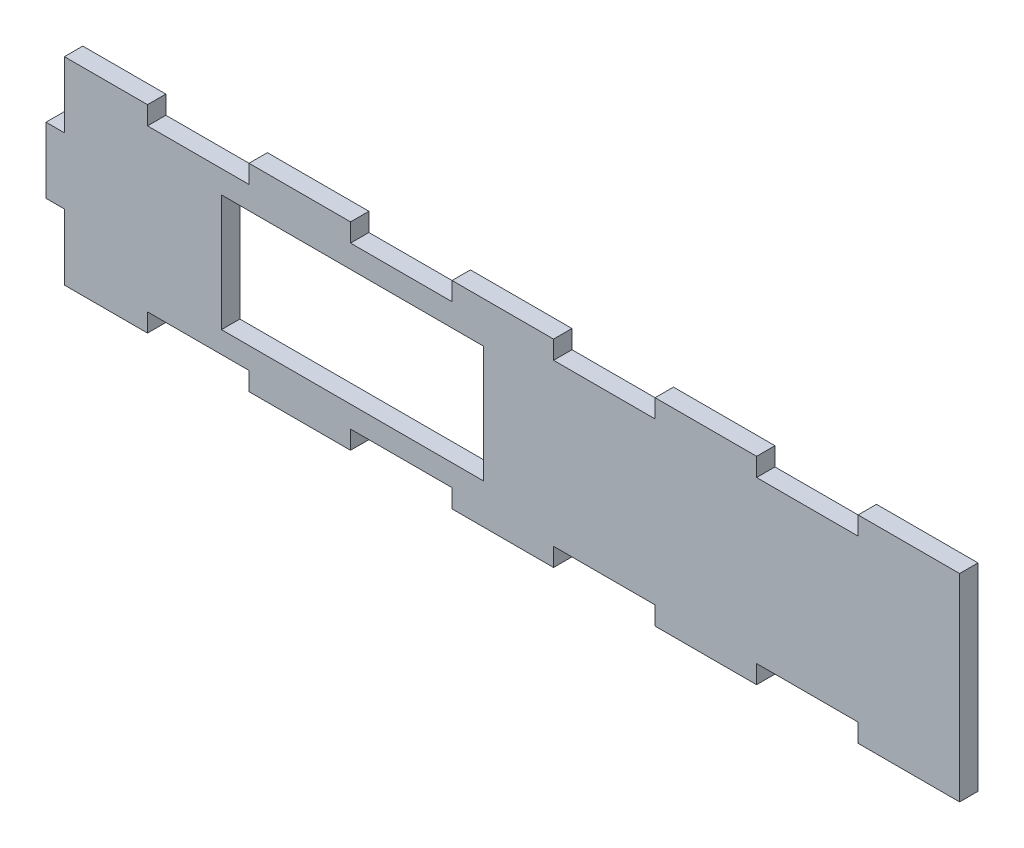
SolidWorks part; units mm, degrees
ref_plane "Front Plane" through (0, 0, 0) normal (0, 0, 1) x (1, 0, 0)
ref_plane "Top Plane" through (0, 0, 0) normal (0, 1, 0) x (1, 0, 0)
ref_plane "Right Plane" through (0, 0, 0) normal (1, 0, 0) x (0, 0, -1)
sketch "Sketch2" plane through (0, 0, 0) normal (0, 0, 1) x (1, 0, 0)
  line L1 (0, 0) -> (228.6, 0)
  line L2 (0, 0) -> (0, 49.5)
  line L3 (0, 49.5) -> (228.6, 49.5)
  line L4 (228.6, 0) -> (228.6, 49.5)
  line L5 (0, 0) -> (228.6, 49.5) construction
  line L6 (0, 49.5) -> (228.6, 0) construction
  point P4 (114.3, 24.75)
  dimension "D1" = 228.6
  dimension "D2" = 49.5
extrude "Boss-Extrude1" add sketch "Sketch2" along normal blind 4.6
sketch "Sketch4" plane through (0, 0, 4.6) normal (0, 0, 1) x (1, 0, 0)
  line L0 (0, 0) -> (228.6, 0) construction
  line L1 (25.4, 0) -> (50.8, 0)
  line L2 (25.4, 0) -> (25.4, 4.6)
  line L3 (25.4, 4.6) -> (50.8, 4.6)
  line L4 (50.8, 0) -> (50.8, 4.6)
  line L5 (25.4, 0) -> (50.8, 4.6) construction
  line L6 (25.4, 4.6) -> (50.8, 0) construction
  line L7 (0, 0) -> (25.4, 0) construction
  line L8 (76.2, 0) -> (101.6, 0)
  line L9 (76.2, 0) -> (76.2, 4.6)
  line L10 (76.2, 4.6) -> (101.6, 4.6)
  line L11 (101.6, 0) -> (101.6, 4.6)
  line L12 (76.2, 0) -> (101.6, 4.6) construction
  line L13 (76.2, 4.6) -> (101.6, 0) construction
  line L14 (127, 0) -> (152.4, 0)
  line L15 (127, 0) -> (127, 4.6)
  line L16 (127, 4.6) -> (152.4, 4.6)
  line L17 (152.4, 0) -> (152.4, 4.6)
  line L18 (127, 0) -> (152.4, 4.6) construction
  line L19 (127, 4.6) -> (152.4, 0) construction
  line L20 (177.8, 0) -> (203.2, 0)
  line L21 (177.8, 0) -> (177.8, 4.6)
  line L22 (177.8, 4.6) -> (203.2, 4.6)
  line L23 (203.2, 0) -> (203.2, 4.6)
  line L24 (177.8, 0) -> (203.2, 4.6) construction
  line L25 (177.8, 4.6) -> (203.2, 0) construction
  line L27 (50.8, 0) -> (76.2, 0) construction
  line L29 (101.6, 0) -> (127, 0) construction
  line L30 (152.4, 0) -> (177.8, 0) construction
  line L31 (203.2, 0) -> (228.6, 0) construction
  point P4 (38.1, 2.3)
  point P11 (88.9, 2.3)
  point P16 (139.7, 2.3)
  point P21 (190.5, 2.3)
  dimension "D2" = 4.6
extrude "Cut-Extrude1" cut sketch "Sketch4" against normal through all
ref_plane "Plane1" through (0, 24.75, 0) normal (0, 1, 0) x (1, 0, 0)
mirror "Mirror1" about plane through (0, 24.75, 0) normal (0, 1, 0) of "Cut-Extrude1"
sketch "Sketch5" plane through (0, 0, 0) normal (-1, 0, 0) x (0, 0, 1)
  line L0 (0, 49.5) -> (0, 0) construction
  line L1 (4.6, 49.5) -> (4.6, 0) construction
  line L2 (0, 16.5) -> (4.6, 16.5)
  line L3 (0, 16.5) -> (0, 33)
  line L4 (0, 33) -> (4.6, 33)
  line L5 (4.6, 16.5) -> (4.6, 33)
  line L6 (0, 16.5) -> (4.6, 33) construction
  line L7 (0, 33) -> (4.6, 16.5) construction
  line L8 (4.6, 49.5) -> (4.6, 33) construction
  line L9 (4.6, 16.5) -> (4.6, 0) construction
  line L11 (4.6, 49.5) -> (0, 49.5)
  line L12 (4.6, 49.5) -> (4.6, 33)
  line L13 (4.6, 33) -> (0, 33)
  line L14 (0, 49.5) -> (0, 33)
  line L15 (0, 16.5) -> (4.6, 16.5)
  line L16 (0, 16.5) -> (0, 0)
  line L17 (0, 0) -> (4.6, 0)
  line L18 (4.6, 16.5) -> (4.6, 0)
  point P6 (2.3, 24.75)
  line M7 (0, 49.5) -> (0, 0)
  line M8 (0, 0) -> (4.6, 0)
  line M9 (4.6, 0) -> (4.6, 49.5)
  line M10 (4.6, 49.5) -> (0, 49.5)
extrude "Cut-Extrude2" cut sketch "Sketch5" against normal blind 4.6 contours L4 M7 M9 M10 | L2 M7 M8 M9 region at (0, 8.25, 2.3) region at (0, 41.25, 2.3)
extrude "Cut-Extrude3" cut sketch "Sketch6" against normal through all
sketch "Sketch6" plane through (29.4576, -124.7153, 49.5) normal (0, 0, 1) x (1, 0, 0)
  line L2 (79.9501, 163.9153) -> (14.4501, 163.9153)
  line L3 (14.4501, 134.7153) -> (79.9501, 134.7153)
  line L4 (79.9501, 134.7153) -> (79.9501, 163.9153)
  line L5 (14.4501, 134.7153) -> (14.4501, 163.9153)
  line L6 (79.9501, 149.3153) -> (14.4501, 149.3153) construction
  point P4 (79.9501, 149.3153)
  point P5 (14.4501, 149.3153)
equation "\"MDF\"= 4.8mm"
equation "\"Foamcore\"= 4.6mm"
equation "\"PCB\" = 1.6mm"
equation "\"GMaterial\"= \"MDF\""
equation "\"BaseWidth\" = 10in"
equation "\"SkidLength\" = 1in"
equation "\"SkidClearance\" = 0.4in"
equation "\"MotorMountLength\" = 2in"
equation "\"MotorMountWidth\" = \"GMaterial\""
equation "\"MotorMountHeight\" = 2.25in"
equation "\"UnoStackWidth\" = 77.4mm"
equation "\"UnoStackLength\" = 79.8mm"
equation "\"UnoStackHeight\" = 34.2mm"
equation "\"TallHexRiserHeight\" = 22.2mm"
equation "\"PingPongBallSize\" = 40mm"
equation "\"BarrelLength\" = 9in"
equation "\"BarrelSize\" = \"PingPongBallSize\""
equation "\"D2@Sketch2\"=\"BarrelSize\"+\"Foamcore\"*2 + \"LaserCutterOffset\""
equation "\"D1@Boss-Extrude1\"=\"Foamcore\""
equation "\"D2@Sketch4\"=\"Foamcore\""
equation "\"D1@Cut-Extrude2\"=\"Foamcore\""
equation "\"PlatformLength\" = 4in"
equation "\"PlatformWidth\" = 6in"
equation "\"WheelDiameter\"=2.99213"
equation "\"ServoMountHeight\"=2.49223"
equation "\"ServoGearHeight\" = 0.95330261in"
equation "\"ServoMountLength\"= 1.53774"
equation "\"PivotHoleRadius\"= 0.616358"
equation "\"PlatformMountHeight\" = 3.19"
equation "\"TensionOffSet\"= .3mm"
equation "\"MotorMountWedge\"=0.333333"
equation "\"LaserCutterOffset\"= .3mm"
equation "\"BumperWidth\"=11"
equation "\"PitcherWheelCompression\" = 2.5mm"
equation "\"PitchingWheelWidth\" = 26.2mm"
equation "\"PitchingWheelDiameter\" = 65.5mm"
equation "\"PitchingWheelMountOffset\" = 8.4mm"
equation "\"PitchingWheelInnerDiameter\" = 45.5mm"
equation "\"PitchingWheelBoltShoulder\" = 4.5mm"
equation "\"BrassCouplingLength\" = 18mm"
equation "\"PitchingMotorHeight\" = 57.0mm"
equation "\"PitchingMotorShaftTopHeight\" = \"PitchingMotorHeight\" - 44.1mm"
equation "\"PitchingMotorBodyHeight\" = 38mm"
equation "\"PitchingMotorTopShoulderHeight\" = 40.6mm - \"PitchingMotorBodyHeight\" "
equation "\"PitchingMotorBottomShoulderHeight\" = 40.2mm - \"PitchingMotorBodyHeight\""
equation "\"PitchingMotorBottomShaftHeight\" = \"PitchingMotorHeight\" - \"PitchingMotorShaftTopHeight\" - \"PitchingMotorTopShoulderHeight\" - \"PitchingMotorBodyHeight\" - \"PitchingMotorBottomShoulderHeight\""
equation "\"PitchingMotorShaftDiameter\" = 2.2mm"
equation "\"PitchingMotorBodyDiameter\" = 27.4mm"
equation "\"PitchingMotorTopShoulderDiameter\" = 9.8mm"
equation "\"PitchingMotorBottomShoulderDiameter\" = 9.8mm"
equation "\"BrassCouplingHexSize\" = 12mm"
equation "\"BrassCouplingBoreSize\" = 3.17mm"
equation "\"PitchingMotorMountingHoleDistance\" = 16mm"
equation "\"Acrylic\" = 4.4mm"
equation "\"PitchingMotorDistance\" = \"PitchingWheelDiameter\" + \"PingPongBallSize\" - \"PitcherWheelCompression\"*2"
equation "\"PitchingMotorPlatformOffset\"=1"
equation "\"ServoPlatformOffset\"=1.64173"
equation "\"BallBearingDiameter\" = 22mm"
equation "\"BallBearingWidth\" = 9mm"
equation "\"BallBearingHexShoulder\" = 9mm - 5.9mm"
equation "\"BallBearingHexSize\" = .36in"
equation "\"PlatformMountFootLength\"=0.857143"
equation "\"WheelWidth\"= 26mm"
equation "\"ServoMountReductionBackHeight\"=2.25"
equation "\"PlatformBottomWidthThird\" =  0.857143in"
equation "\"PlatformMountBackReductionHeight\"= 2.5in"
equation "\"PlatformMountBackReductionWidth\"= 3/7in"
equation "\"PlatformMountFrontReductionWidth\" =  1.46226in"
equation "\"PlatformMountFrontReductionHeight\" = 2.5in"
